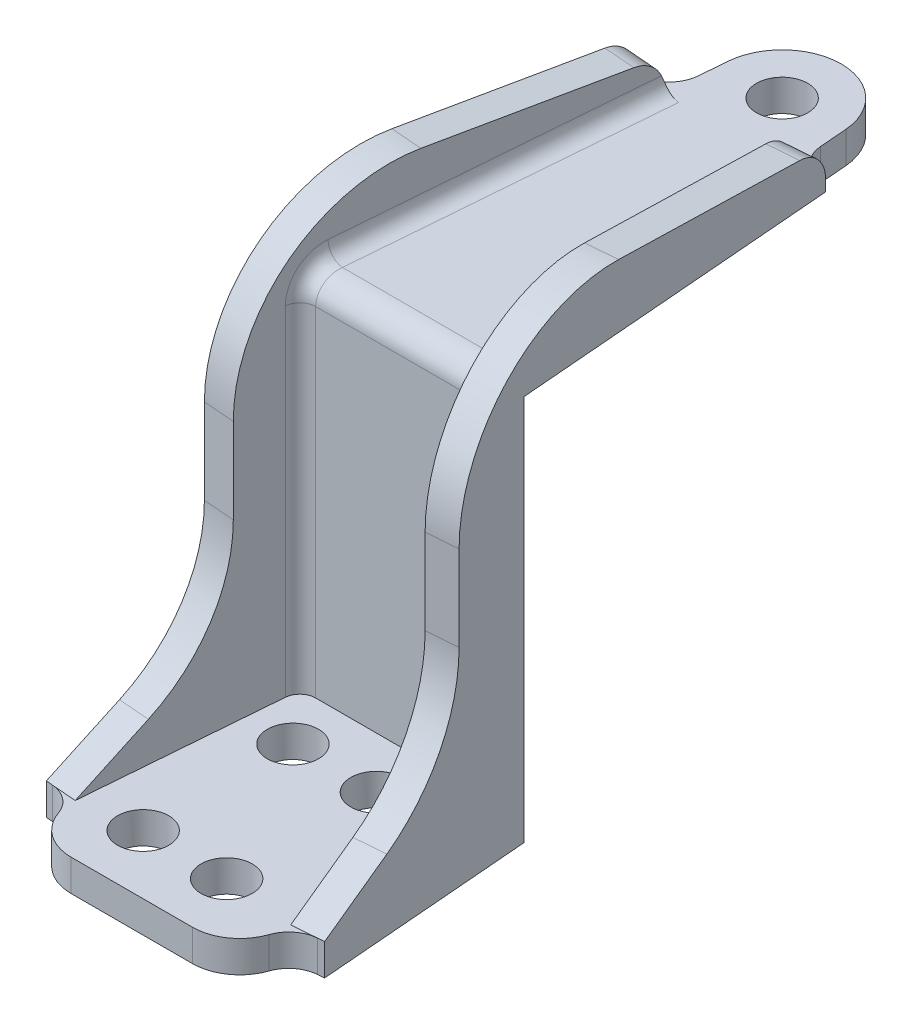
SolidWorks part; units mm, degrees
material "Plain Carbon Steel"
ref_plane "Front Plane" through (0, 0, 0) normal (0, 0, 1) x (1, 0, 0)
ref_plane "Top Plane" through (0, 0, 0) normal (0, 1, 0) x (1, 0, 0)
ref_plane "Right Plane" through (0, 0, 0) normal (1, 0, 0) x (0, 0, -1)
sketch "Sketch1" plane through (0, 0, 0) normal (1, 0, 0) x (0, 0, -1)
  line L0 (0, 0) -> (-54, 0)
  line L1 (-55, -1) -> (-55, -45)
  line L2 (-56, -46) -> (-90, -46)
  arc A0 (-55, -45) -> (-56, -46) centre (-56, -45) cw
  arc A1 (-54, 0) -> (-55, -1) centre (-54, -1) ccw
  point P7 (-55, -46)
  point P10 (-55, 0)
  dimension "D4" = 1
  dimension "D1" = 46
  dimension "D2" = 35
  dimension "D3" = 55
extrude "Extrude-Thin1" add sketch "Sketch1" along normal mid plane 30 thin
sketch "Sketch2" plane through (0, 2, 0) normal (0, 1, 0) x (1, 0, 0)
  line L0 (-15, -73.5) -> (15, -73.5) construction
  line L1 (15, -57) -> (15, -90) construction
  line L2 (-15, -57) -> (-15, -90) construction
  line L3 (15, -56) -> (-15, -56) construction
  line L6 (-6.0613, -82.5) -> (-6.0613, -63.5) construction
  line L7 (-6.0613, -63.5) -> (4.5257, -63.5) construction
  line L8 (4.5257, -63.5) -> (4.5257, -82.5) construction
  line L9 (4.5257, -82.5) -> (-6.0613, -82.5) construction
  line L13 (15, -90) -> (-15, -90) construction
  line L15 (0, -7.5) -> (0, 0) construction
  line L16 (15, 0) -> (-15, 0) construction
  line L17 (-7.4756, -6.8958) -> (-15, -100)
  line L18 (-15, 0) -> (-15, -54) construction
  line L19 (7.4756, -6.8958) -> (15, -100)
  line L20 (-15, -100) -> (-17.6002, 8.4483)
  line L21 (-17.6002, 8.4483) -> (38.4266, 9.4295)
  line L22 (38.4266, 9.4295) -> (15, -100)
  circle A0 centre (0, -7.5) radius 3.25
  arc A1 (7.4756, -6.8958) -> (-7.4756, -6.8958) centre (0, -7.5) ccw
  circle A3 centre (-6.0613, -82.5) radius 3.25
  circle A4 centre (-6.0613, -63.5) radius 3.25
  circle A5 centre (4.5257, -82.5) radius 3.25
  circle A6 centre (4.5257, -63.5) radius 3.25
  circle A7 centre (4.5257, -63.5) radius 7.5 construction
  circle A8 centre (-6.0613, -82.5) radius 7.5 construction
  dimension "D1" = 6.5
  dimension "D2" = 6.5
  dimension "D3" = 15
  dimension "D4" = 15
  dimension "D5" = 100
extrude "Cut-Extrude1" cut sketch "Sketch2" against normal through all
fillet "Fillet1" radius 6 2 edges at (14.1918, -46, 90) (-14.1918, -46, 90)
sketch "Sketch8" plane through (6.8734, 0, -0.5555) normal (0.9968, 0, -0.0806) x (-0.0806, 0, -0.9968)
  line L0 (-7.4756, 2) -> (0.0244, 2) construction
  line L3 (-53.7301, -45) -> (-53.7301, -2) construction
  line L4 (-53.7301, -2) -> (-7.4756, -2) construction
  line L5 (-56.7399, -48) -> (-84.3463, -48)
  line L6 (-53.7301, -45) -> (-53.7301, -2)
  line L7 (-53.7301, -2) -> (-14.9756, -2)
  line L8 (-14.9756, 2) -> (-14.9756, -2)
  line L9 (-7.4756, 2) -> (-14.9756, 2) construction
  line L10 (-7.4756, 2) -> (-54.7334, 2) construction
  line L11 (-14.9756, 2) -> (-14.9756, 2.3977)
  line L12 (-18.5583, 6.3759) -> (-43.6433, 9.0076)
  line L13 (-65.7301, -10.8832) -> (-65.7301, -21.7049)
  line L14 (-75.7301, -39.0255) -> (-84.3463, -44)
  line L15 (-84.3463, -44) -> (-84.3463, -48)
  arc A0 (-65.7301, -21.7049) -> (-75.7301, -39.0255) centre (-85.7301, -21.7049) cw
  arc A1 (-43.6433, 9.0076) -> (-65.7301, -10.8832) centre (-45.7301, -10.8832) ccw
  arc A2 (-14.9756, 2.3977) -> (-18.5583, 6.3759) centre (-18.9756, 2.3977) ccw
  ellipse E1 centre (-56.7399, -45) end of major axis (-53.7301, -45) minor radius 3 (-56.7399, -48) -> (-53.7301, -45) ccw construction
  ellipse E3 centre (-56.7399, -45) end of major axis (-53.7301, -45) minor radius 3 (-56.7399, -48) -> (-53.7301, -45) ccw
  point P46 (-14.9756, 6)
  dimension "D3" = 20
  dimension "D6" = 4
  dimension "D1" = 4
  dimension "D2" = 12
  dimension "D4" = 12
  dimension "D5" = 30
extrude "Boss-Extrude1" add sketch "Sketch8" along normal blind 4
mirror "Mirror1" about plane through (0, 0, 0) normal (1, 0, 0) of "Boss-Extrude1"
fillet "Fillet2" radius 4 4 edges at (13.6679, -46, 83.5167) (-13.6679, -46, 83.5167)
fillet "Fillet3" radius 2 6 edges at (-11.5249, -22.5, 57) (-11.4539, 1.1213, 56.1213) (11.5249, -22.5, 57) (11.4539, 1.1213, 56.1213) (-9.6811, 2, 34.1857) (9.6811, 2, 34.1857)
chamfer "Chamfer1" distance 3 angle 45 4 edges at (15.1886, -23.5, 52.6778) (-15.1886, -23.5, 52.6778) (13.6277, -2, 33.3635) (-13.6277, -2, 33.3635)
